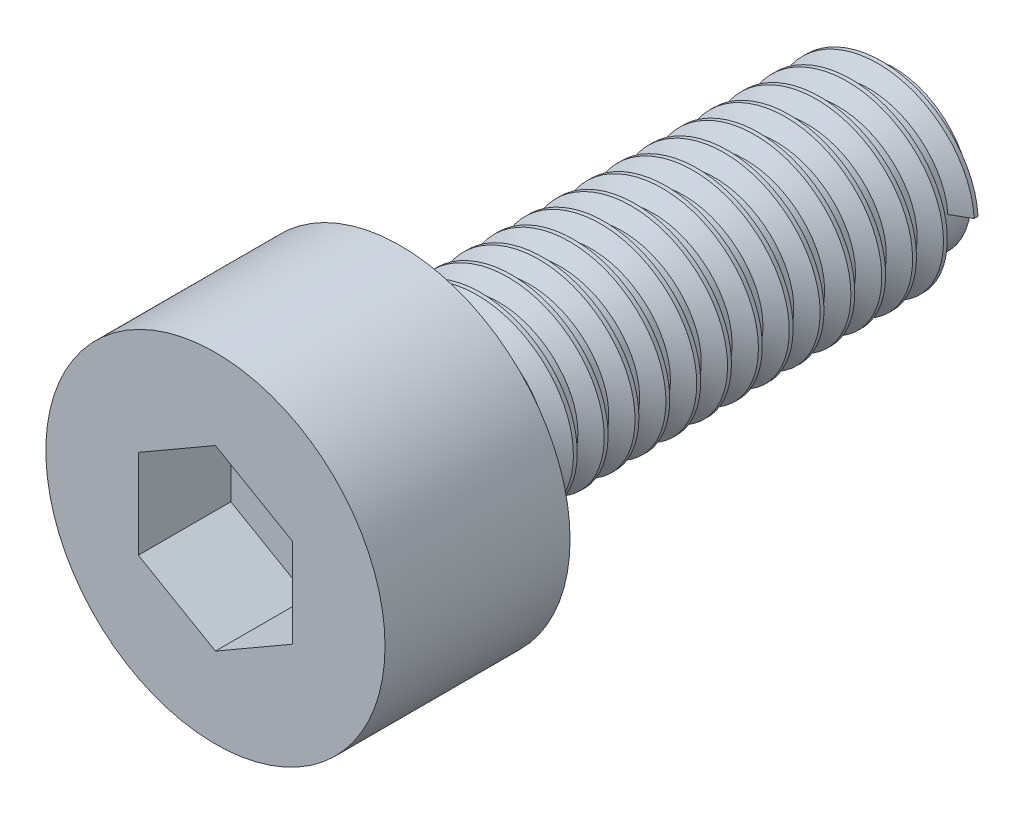
SolidWorks part; units mm, degrees
material "Cast Carbon Steel"
ref_plane "Front Plane" through (0, 0, 0) normal (0, 0, 1) x (1, 0, 0)
ref_plane "Top Plane" through (0, 0, 0) normal (0, 1, 0) x (1, 0, 0)
ref_plane "Right Plane" through (0, 0, 0) normal (1, 0, 0) x (0, 0, -1)
sketch "Sketch1" plane through (0, 0, 0) normal (0, 0, 1) x (1, 0, 0)
  circle A0 centre (0, 0) radius 2.75
  dimension "D1" = 5.5
extrude "Boss-Extrude1" add sketch "Sketch1" along normal blind 3
sketch "Sketch2" plane through (0, 0, 0) normal (0, 0, -1) x (-1, 0, 0)
  circle A0 centre (0, 0) radius 1.25
  dimension "D1" = 2.5
extrude "Boss-Extrude2" add sketch "Sketch2" along normal blind 8
sketch "Sketch3" plane through (0, 0, 3) normal (0, 0, 1) x (1, 0, 0)
  line L1 (0, 1.4434) -> (-1.25, 0.7217)
  line L2 (-1.25, 0.7217) -> (-1.25, -0.7217)
  line L3 (-1.25, -0.7217) -> (0, -1.4434)
  line L4 (0, -1.4434) -> (1.25, -0.7217)
  line L5 (1.25, -0.7217) -> (1.25, 0.7217)
  line L6 (1.25, 0.7217) -> (0, 1.4434)
  circle A0 centre (0, 0) radius 1.25 construction
  dimension "D1" = 2.5
extrude "Cut-Extrude1" cut sketch "Sketch3" against normal blind 1.5
thread "Thread1" pitch 0.5 method extrude profile "Thread Profile1" start angle 0, offset 0, length 8, pitch 0.5, diameter 2.5
ref_plane "Plane1" through (1.25, 0, -8) normal (0, -1, 0) x (1, 0, 0)
sketch "Thread Profile1" plane through (1.25, 0, -8) normal (0, -1, 0) x (1, 0, 0)
  line L0 (0, 0) -> (0, 0.5) construction
  line L1 (0, 0) -> (0.2706, 0.1562)
  line L2 (0.2706, 0.1562) -> (0.2706, 0.2187)
  line L3 (0.2706, 0.2187) -> (0, 0.375)
  line L4 (0.2706, 0.1875) -> (0, 0.1875) construction
  line L11 (0, 0) -> (0, 0.375)
  point P2 (0, 0)
  dimension "Pitch" = 0.5
  dimension "Profile_Angle" = 60
  dimension "Profile_Land" = 0.0625
  dimension "Profile_Height" = 0.2706
